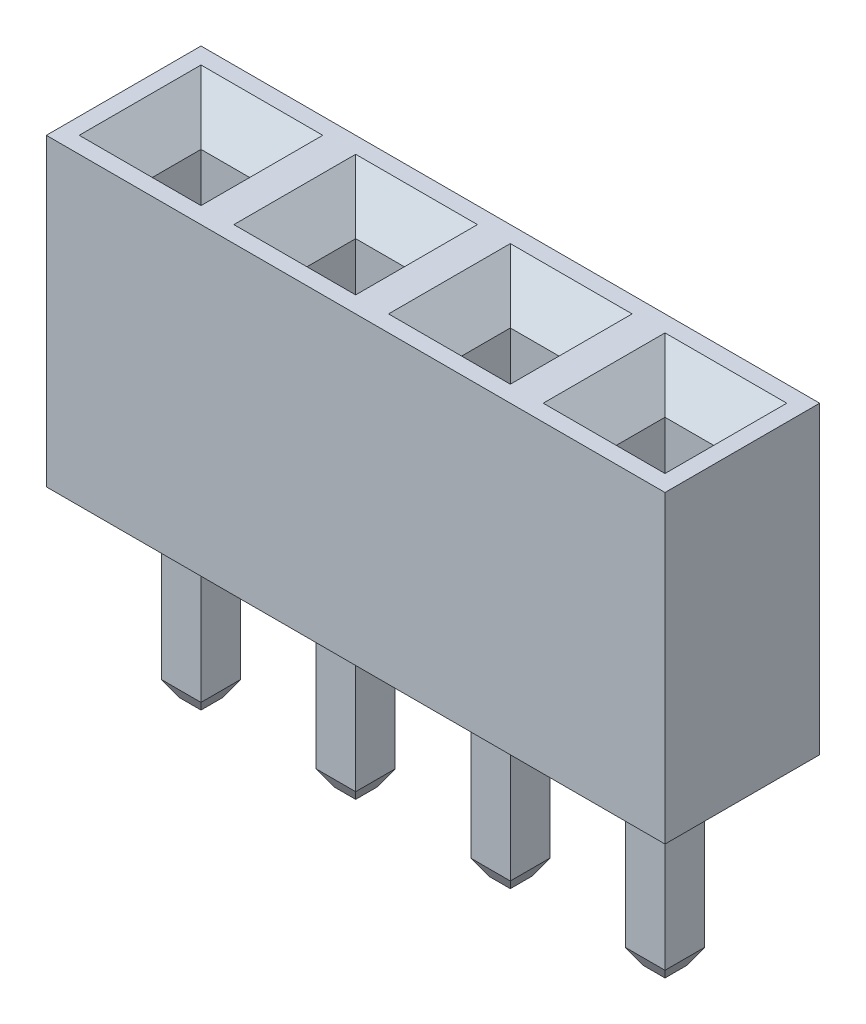
SolidWorks part; units mm, degrees
ref_plane "Front Plane" through (0, 0, 0) normal (0, 0, 1) x (1, 0, 0)
ref_plane "Top Plane" through (0, 0, 0) normal (0, 1, 0) x (1, 0, 0)
ref_plane "Right Plane" through (0, 0, 0) normal (1, 0, 0) x (0, 0, -1)
sketch "Sketch1" plane through (0, 0, 0) normal (0, 1, 0) x (1, 0, 0)
  line L1 (-1.27, 1.27) -> (1.27, 1.27)
  line L2 (-1.27, 1.27) -> (-1.27, -1.27)
  line L3 (-1.27, -1.27) -> (1.27, -1.27)
  line L4 (1.27, 1.27) -> (1.27, -1.27)
  line L5 (-1.27, 1.27) -> (1.27, -1.27) construction
  line L6 (-1.27, -1.27) -> (1.27, 1.27) construction
  point P0 (0, 0)
  dimension "D1" = 2.54
extrude "Boss-Extrude1" add sketch "Sketch1" along normal blind 5
sketch "Sketch2" plane through (0, 0, 0) normal (0, -1, 0) x (1, 0, 0)
  line L1 (-0.325, 0.325) -> (0.325, 0.325)
  line L2 (-0.325, 0.325) -> (-0.325, -0.325)
  line L3 (-0.325, -0.325) -> (0.325, -0.325)
  line L4 (0.325, 0.325) -> (0.325, -0.325)
  line L5 (-0.325, 0.325) -> (0.325, -0.325) construction
  line L6 (-0.325, -0.325) -> (0.325, 0.325) construction
  point P0 (0, 0)
  dimension "D1" = 0.65
extrude "Boss-Extrude2" add sketch "Sketch2" along normal blind 3
chamfer "Chamfer1" distance 0.15 angle 60 4 edges at (0, -3, -0.325) (-0.325, -3, 0) (0, -3, 0.325) (0.325, -3, 0) first distance on face at (0, -3, 0)
sketch "Sketch3" plane through (0, 5, 0) normal (0, 1, 0) x (1, 0, 0)
  line L1 (-0.4, 0.4) -> (0.4, 0.4)
  line L2 (-0.4, 0.4) -> (-0.4, -0.4)
  line L3 (-0.4, -0.4) -> (0.4, -0.4)
  line L4 (0.4, 0.4) -> (0.4, -0.4)
  line L5 (-0.4, 0.4) -> (0.4, -0.4) construction
  line L6 (-0.4, -0.4) -> (0.4, 0.4) construction
  point P0 (0, 0)
  dimension "D1" = 0.8
extrude "Cut-Extrude1" cut sketch "Sketch3" against normal blind 3
chamfer "Chamfer2" distance 0.6 angle 45 4 edges at (-0.4, 5, 0) (0, 5, 0.4) (0.4, 5, 0) (0, 5, -0.4)
pattern_linear "LPattern1" count 4 spacing 2.54 along (1, 0, 0) of "Boss-Extrude1", "Boss-Extrude2", "Cut-Extrude1", "Chamfer2", "Chamfer1"
ref_axis "Axis1" through (0, -5.675, 0) along (0, 1, 0)
